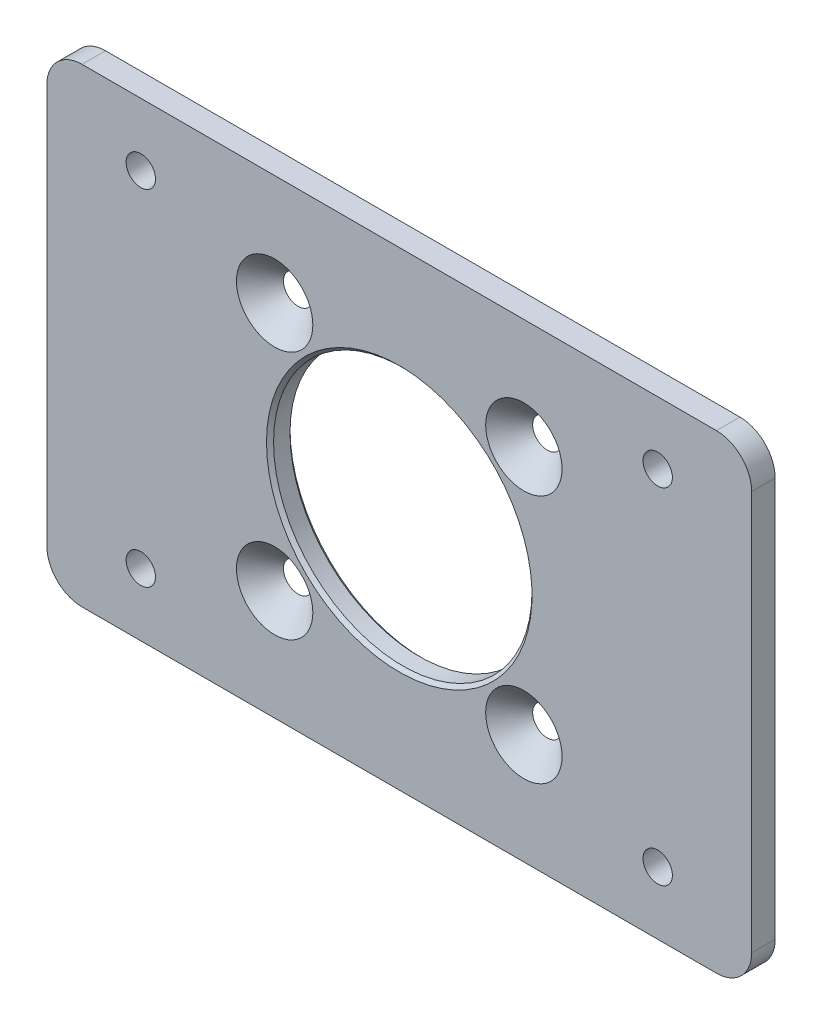
SolidWorks part; units mm, degrees
ref_plane "Płaszczyzna przednia" through (0, 0, 0) normal (0, 0, 1) x (1, 0, 0)
ref_plane "Płaszczyzna górna" through (0, 0, 0) normal (0, 1, 0) x (1, 0, 0)
ref_plane "Płaszczyzna prawa" through (0, 0, 0) normal (1, 0, 0) x (0, 0, -1)
sketch "Szkic1" plane through (0, 0, 0) normal (0, 0, 1) x (1, 0, 0)
  line L0 (0, 0) -> (-23.297, 23.297) construction
  line L1 (-27, -20) -> (27, -20)
  line L2 (-30, -17) -> (-30, 17)
  line L3 (-27, 20) -> (27, 20)
  line L4 (30, -17) -> (30, 17)
  line L5 (-30, -20) -> (30, 20) construction
  line L6 (-30, 20) -> (30, -20) construction
  line L7 (0, 0) -> (25.2349, 25.2349) construction
  arc A0 (27, 20) -> (30, 17) centre (27, 17) cw
  arc A1 (27, -20) -> (30, -17) centre (27, -17) ccw
  arc A2 (-27, -20) -> (-30, -17) centre (-27, -17) cw
  arc A3 (-30, 17) -> (-27, 20) centre (-27, 17) cw
  circle A4 centre (0, 0) radius 11
  circle A5 centre (-22, 14.6667) radius 1.25
  circle A6 centre (22, 14.6667) radius 1.25
  circle A7 centre (22, -14.6667) radius 1.25
  circle A8 centre (-10.6066, -10.6066) radius 1.25
  circle A9 centre (10.6066, -10.6066) radius 1.25
  circle A10 centre (10.6066, 10.6066) radius 1.25
  circle A11 centre (-10.6066, 10.6066) radius 1.25
  circle A12 centre (0, 0) radius 15 construction
  circle A13 centre (-22, -14.6667) radius 1.25
  point P0 (0, 0)
  dimension "D3" = 3
  dimension "D4" = 30
  dimension "D6" = 2.5
  dimension "D7" = 2.5
  dimension "D8" = 2.5
  dimension "D9" = 2.5
  dimension "D10" = 22
  dimension "D11" = 2.5
  dimension "D1" = 60
  dimension "D2" = 40
  dimension "D5" = 45
  dimension "D12" = 8
extrude "Dodanie-wyciągnięcie1" add sketch "Szkic1" along normal blind 2
chamfer "Sfazowanie1" distance 0.3 angle 45 2 edges at (11, 0, 0) (11, 0, 2)
chamfer "Sfazowanie2" distance 2 angle 45 4 edges at (-9.3566, -10.6066, 2) (11.8566, -10.6066, 2) (11.8566, 10.6066, 2) (-9.3566, 10.6066, 2)
sketch "Szkic2" plane through (0, 0, 2) normal (0, 0, 1) x (1, 0, 0)
  line L9 (26.6537, 22.5572) -> (-27.2723, 19.731)
  line L10 (-30.1112, 16.5781) -> (-28.3317, -17.3753)
  line L11 (-25.1788, -20.2142) -> (28.7472, -17.388)
  line L12 (31.586, -14.2351) -> (29.8066, 19.7183)
  arc A8 (29.8066, 19.7183) -> (26.6537, 22.5572) centre (26.8107, 19.5613) ccw
  arc A9 (-27.2723, 19.731) -> (-30.1112, 16.5781) centre (-27.1153, 16.7351) ccw
  arc A10 (-28.3317, -17.3753) -> (-25.1788, -20.2142) centre (-25.3358, -17.2183) ccw
  arc A11 (28.7472, -17.388) -> (31.586, -14.2351) centre (28.5902, -14.3921) ccw
equation "\"D7@Szkic1\"=\"D6@Szkic1\""
equation "\"D8@Szkic1\"=\"D6@Szkic1\""
equation "\"D9@Szkic1\"=\"D6@Szkic1\""
